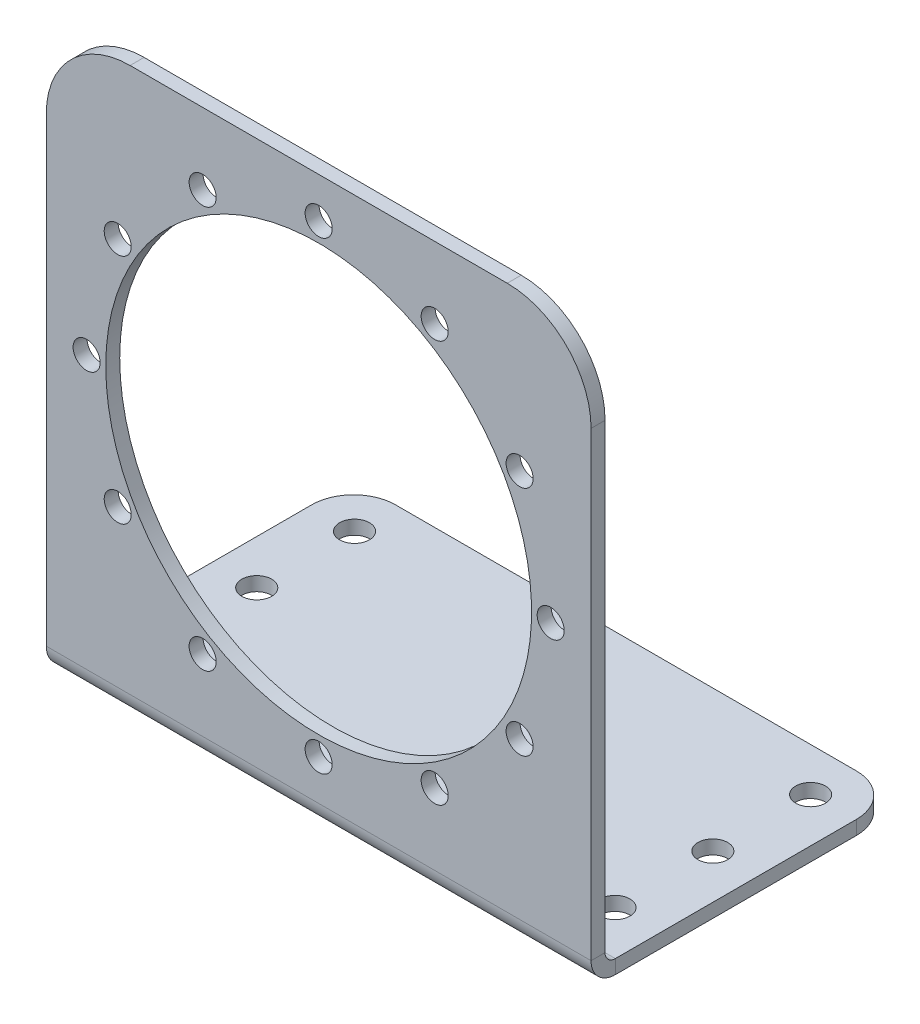
SolidWorks part; units mm, degrees
note: The reader was unsure of these and kept them because the rebuilt part matched: flange length of "Edge-Flange1".
ref_plane "Front Plane" through (0, 0, 0) normal (0, 0, 1) x (1, 0, 0)
ref_plane "Top Plane" through (0, 0, 0) normal (0, 1, 0) x (1, 0, 0)
ref_plane "Right Plane" through (0, 0, 0) normal (1, 0, 0) x (0, 0, -1)
other "Center of Mass"
sketch "Sketch2" plane through (0, 0, 0) normal (0, 0, 1) x (1, 0, 0)
  line L1 (0, 0) -> (39, 0)
  line L2 (0, 0) -> (0, 33)
  line L3 (6, 39) -> (33, 39)
  line L4 (39, 0) -> (39, 33)
  arc A0 (39, 33) -> (33, 39) centre (33, 33) ccw
  arc A1 (6, 39) -> (0, 33) centre (6, 33) ccw
  point P7 (39, 39)
  point P10 (0, 39)
  dimension "D3" = 6
  dimension "D1" = 39
  dimension "D2" = 39
base flange "Base-Flange1" sketch "Sketch2" thickness 1 reverse thickness direction no parameters "D1"=0.7366
edge flange "Edge-Flange1" sketch "Sketch11" flange angle 90 flange length 22 flange position bend outside bend radius 0.7366 thickness 1 relief rectangular parameters "D6"=10
sketch "Sketch11" plane through (0, 0, -1) normal (0, -1, 0) x (-1, 0, 0)
  line L2 (-39, 0) -> (-39, 21)
  line L3 (-39, 21) -> (0, 21)
  line L4 (0, 21) -> (0, 0)
  line L5 (0, 0) -> (-39, 0) construction
  line L6 (0, 0) -> (-39, 0)
bend "EdgeBend1" bend radius 0.7366 bend angle 90 parameters "D5"=1
fillet "Fillet1" radius 3 2 edges at (39, -1.2366, -22) (0, -1.2366, -22)
sketch "Sketch12" plane through (0, 0, -1) normal (0, 0, -1) x (-1, 0, 0)
  line L0 (-19.5, 39) -> (-19.5, 0) construction
  line L1 (-33, 39) -> (-6, 39) construction
  line L2 (0, 0) -> (-39, 0) construction
  line L3 (0, 16.5) -> (-39, 16.5) construction
  line L4 (0, 33) -> (0, 0) construction
  line L5 (-39, 0) -> (-39, 33) construction
  circle A0 centre (-19.5, 19.5) radius 15.242
  circle A1 centre (-19.5, 36.1104) radius 0.9685
  circle A2 centre (-27.8052, 33.8851) radius 0.9685
  circle A3 centre (-33.8851, 27.8052) radius 0.9685
  circle A4 centre (-36.1104, 19.5) radius 0.9685
  circle A5 centre (-33.8851, 11.1948) radius 0.9685
  circle A6 centre (-27.8052, 5.1149) radius 0.9685
  circle A7 centre (-19.5, 2.8896) radius 0.9685
  circle A8 centre (-11.1948, 5.1149) radius 0.9685
  circle A9 centre (-5.1149, 11.1948) radius 0.9685
  circle A10 centre (-2.8896, 19.5) radius 0.9685
  circle A11 centre (-5.1149, 27.8052) radius 0.9685
  circle A12 centre (-11.1948, 33.8851) radius 0.9685
  point P41 (-19.5, 19.5)
  dimension "D1" = 12
extrude "Cut-Extrude1" cut sketch "Sketch12" against normal blind 1 normal cut yes
sketch "Sketch13" plane through (0, -0.7366, 0) normal (0, 1, 0) x (1, 0, 0)
  line L0 (19.5, 22) -> (19.5, 1.7366) construction
  line L1 (3, 22) -> (36, 22) construction
  line L2 (39, 1.7366) -> (0, 1.7366) construction
  circle A0 centre (3.1755, 18.8916) radius 1.0666
  circle A1 centre (3.1755, 11.8916) radius 1.0666
  circle A2 centre (3.1755, 4.8916) radius 1.0666
  circle A3 centre (35.8245, 4.8916) radius 1.0666
  circle A4 centre (35.8245, 11.8916) radius 1.0666
  circle A5 centre (35.8245, 18.8916) radius 1.0666
  dimension "D1" = 3
extrude "Cut-Extrude2" cut sketch "Sketch13" against normal blind 1 normal cut yes
sketch "Bend-Lines1" [suppressed] plane through (0, 0, 0) normal (0, 1, 0) x (1, 0, 0)
sketch "Bounding-Box1" [suppressed] plane through (0, 0, 0) normal (0, 1, 0) x (1, 0, 0)
sheet metal parameters "Sheet-Metal2" thickness 1 parameters "D1"=0.7366
flat pattern "Flat-Pattern2" [suppressed]
sketch "Bend-Lines2" plane through (0, 0, 0) normal (0, 1, 0) x (1, 0, 0)
sketch3d "Bounding-Box2" [suppressed]
  line L0 (-33, -33, 0) -> (-33, 6, 0) construction
  line L1 (6, -33, 0) -> (6, 6, 0) construction
  line L2 (-33, -33, 0) -> (6, -33, 0) construction
  line L3 (-33, 6, 0) -> (6, 6, 0) construction
sheet metal parameters "Sheet-Metal3" thickness 1 parameters "D1"=0.7366
flat pattern "Flat-Pattern2"
sketch "Bend-Lines2" plane through (0, 0, 0) normal (0, 0, 1) x (1, 0, 0)
  line L0 (0, -0.9712) -> (39, -0.9712) construction
  line L1 (0, -0.9712) -> (39, -0.9712) construction
sketch3d "Bounding-Box2" [suppressed]
  line L0 (33, -55.2058, 0) -> (33, 6, 0) construction
  line L1 (-6, -55.2058, 0) -> (-6, 6, 0) construction
  line L2 (33, -55.2058, 0) -> (-6, -55.2058, 0) construction
  line L3 (33, 6, 0) -> (-6, 6, 0) construction
bend of the flat pattern "Flatten-<EdgeBend1>1"
sheet metal parameters "Sheet-Metal4" thickness 1 parameters "D1"=0.7366
flat pattern "Flat-Pattern2"
sketch "Bend-Lines2" plane through (0, 0, 0) normal (0, 0, 1) x (1, 0, 0)
  line L0 (0, -0.9712) -> (39, -0.9712) construction
  line L1 (0, -0.9712) -> (39, -0.9712) construction
sketch3d "Bounding-Box2" [suppressed]
  line L0 (33, -55.2058, 0) -> (33, 6, 0) construction
  line L1 (-6, -55.2058, 0) -> (-6, 6, 0) construction
  line L2 (33, -55.2058, 0) -> (-6, -55.2058, 0) construction
  line L3 (33, 6, 0) -> (-6, 6, 0) construction
bend of the flat pattern "Flatten-<EdgeBend1>1"
sheet metal parameters "Sheet-Metal5" thickness 1 parameters "D1"=0.7366
flat pattern "Flat-Pattern2"
sketch "Bend-Lines2" plane through (0, 0, 0) normal (0, 0, 1) x (1, 0, 0)
  line L0 (0, -0.9712) -> (39, -0.9712) construction
  line L1 (0, -0.9712) -> (39, -0.9712) construction
sketch3d "Bounding-Box2" [suppressed]
  line L0 (33, -55.2058, 0) -> (33, 6, 0) construction
  line L1 (-6, -55.2058, 0) -> (-6, 6, 0) construction
  line L2 (33, -55.2058, 0) -> (-6, -55.2058, 0) construction
  line L3 (33, 6, 0) -> (-6, 6, 0) construction
bend of the flat pattern "Flatten-<EdgeBend1>1"
